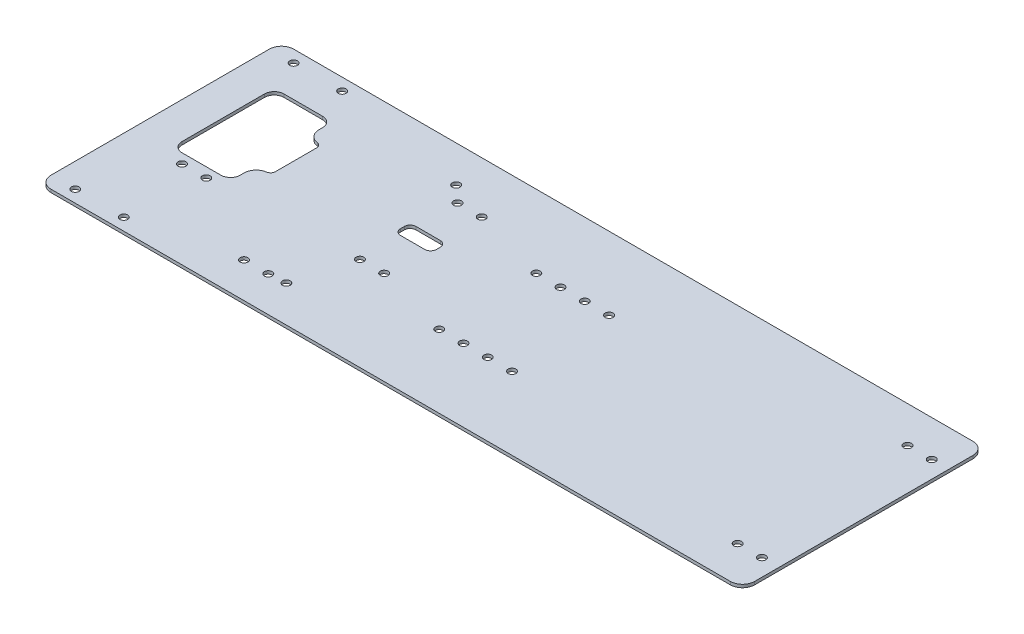
SolidWorks part; units mm, degrees
ref_plane "Front Plane" through (0, 0, 0) normal (0, 0, 1) x (1, 0, 0)
ref_plane "Top Plane" through (0, 0, 0) normal (0, 1, 0) x (1, 0, 0)
ref_plane "Right Plane" through (0, 0, 0) normal (1, 0, 0) x (0, 0, -1)
sketch "Sketch1" plane through (0, 0, 0) normal (0, 1, 0) x (1, 0, 0)
  line L0 (128.27, 0) -> (-128.27, 0) construction
  line L1 (184.15, 63.5) -> (-184.15, 63.5)
  line L2 (184.15, 63.5) -> (184.15, -63.5)
  line L3 (184.15, -63.5) -> (-184.15, -63.5)
  line L4 (-184.15, 63.5) -> (-184.15, -63.5)
  line L5 (184.15, 63.5) -> (-184.15, -63.5) construction
  line L6 (184.15, -63.5) -> (-184.15, 63.5) construction
  line L7 (-128.27, 0) -> (-128.27, 31.75) construction
  line L8 (-128.27, 31.75) -> (-134.62, 31.75) construction
  line L9 (-128.27, 6.35) -> (-134.62, 6.35) construction
  line L12 (-165.1, -12.7) -> (-165.1, 40.64)
  line L15 (-134.62, -12.7) -> (-165.1, -12.7)
  line L17 (-134.62, 40.64) -> (-165.1, 40.64)
  line L18 (0, 63.5) -> (0, -63.5) construction
  line L19 (-134.62, 40.64) -> (-134.62, -12.7)
  line L21 (-95.25, -45.0215) -> (-95.25, -32.3215) construction
  line L22 (-82.55, -45.0215) -> (-95.25, -45.0215) construction
  line L25 (128.27, 31.75) -> (128.27, 6.35) construction
  line L26 (-95.25, -32.3215) -> (-82.55, -32.3215) construction
  line L30 (-82.55, -32.3215) -> (-82.55, -45.0215) construction
  line L31 (184.15, -17.78) -> (154.94, -17.78) construction
  line L32 (146.05, 57.15) -> (184.15, 57.15) construction
  line L33 (154.94, -17.78) -> (142.24, -17.78) construction
  line L34 (146.05, -57.15) -> (184.15, -57.15) construction
  line L35 (-146.05, -57.15) -> (-184.15, -57.15) construction
  line L36 (-146.05, 57.15) -> (-184.15, 57.15) construction
  line L37 (-128.27, 0) -> (-128.27, 6.35) construction
  line L38 (-184.15, -17.78) -> (-154.94, -17.78) construction
  line L39 (-154.94, -17.78) -> (-142.24, -17.78) construction
  line L40 (-134.62, 27.305) -> (-127, 27.305)
  line L41 (-127, 27.305) -> (-127, 0.635)
  line L42 (-127, 0.635) -> (-134.62, 0.635)
  circle A4 centre (171.45, 31.75) radius 2.032 construction
  circle A5 centre (128.27, 31.75) radius 2.032 construction
  circle A6 centre (128.27, 6.35) radius 2.032 construction
  circle A7 centre (171.45, -3.81) radius 2.032 construction
  circle A8 centre (171.45, -57.15) radius 2.032
  circle A9 centre (146.05, -57.15) radius 2.032
  circle A10 centre (171.45, 57.15) radius 2.032
  circle A11 centre (146.05, 57.15) radius 2.032
  circle A12 centre (-146.05, -57.15) radius 2.032
  circle A13 centre (-171.45, -57.15) radius 2.032
  circle A14 centre (-146.05, 57.15) radius 2.032
  circle A15 centre (-171.45, 57.15) radius 2.032
  circle A16 centre (142.24, -17.78) radius 2.032 construction
  circle A17 centre (154.94, -17.78) radius 2.032 construction
  circle A18 centre (-154.94, -17.78) radius 2.032
  circle A19 centre (-142.24, -17.78) radius 2.032
  circle A20 centre (-95.25, -45.0215) radius 2.032
  circle A21 centre (-82.55, -45.0215) radius 2.032
  circle A22 centre (-95.25, -32.3215) radius 2.032
  circle A23 centre (-82.55, -32.3215) radius 2.032
  point P0 (0, 0)
  point P11 (-128.27, 0)
  point P13 (-134.62, 31.75)
  point P17 (-134.62, 6.35)
  point P37 (0, 0)
  point P50 (171.45, 57.15)
  point P51 (146.05, 57.15)
  point P56 (171.45, -57.15)
  point P57 (146.05, -57.15)
  point P84 (-130.81, 27.305)
  point P87 (130.81, 27.305)
  dimension "D5" = 13.335
  dimension "D18" = 4.064
  dimension "D1" = 368.3
  dimension "D2" = 127
  dimension "D3" = 128.27
  dimension "D4" = 25.4
  dimension "D7" = 6.35
  dimension "D8" = 30.48
  dimension "D9" = 53.34
  dimension "D10" = 8.89
  dimension "D11" = 19.05
  dimension "D14" = 12.7
  dimension "D15" = 38.1
  dimension "D16" = 12.7
  dimension "D17" = 38.1
  dimension "D19" = 31.75
  dimension "D20" = 6.35
  dimension "D21" = 6.35
  dimension "D22" = 5.08
  dimension "D23" = 29.21
  dimension "D24" = 12.7
  dimension "D25" = 88.9
  dimension "D26" = 12.7
  dimension "D27" = 7.62
  dimension "D28" = 26.67
  dimension "D29" = 13.335
  dimension "D30" = 18.4785
  dimension "D31" = 12.7
extrude "Boss-Extrude1" add sketch "Sketch1" along normal blind 1.5875 contours L1 L4 L3 L2 A23 A22 A21 A20 A18 A14 A12 A11 A10 A9 A8 L41 L42 L19 L15 L12 L17 L40 A13 A15 A19 | A9 | A8 | A11 | A10 | A22 | A23 region at (6.2259, 0, 0.5157) region at (171.45, 0, 57.15) region at (146.05, 0, 57.15) region at (171.45, 0, -57.15) region at (146.05, 0, -57.15) region at (-95.25, 0, 32.3215) region at (-82.55, 0, 32.3215)
sketch "Sketch2" [suppressed] plane through (0, 1.5875, 0) normal (0, 1, 0) x (1, 0, 0)
  line L0 (-69.85, 63.5) -> (-69.85, -63.5)
  line L1 (184.15, 63.5) -> (-184.15, 63.5) construction
  line L2 (184.15, -63.5) -> (-184.15, -63.5) construction
  circle A0 centre (-82.55, -45.0215) radius 2.032 construction
  circle M9 centre (146.05, 57.15) radius 2.032
  circle M10 centre (171.45, 57.15) radius 2.032
  circle M11 centre (146.05, -57.15) radius 2.032
  circle M12 centre (171.45, -57.15) radius 2.032
  line M13 (184.15, 63.5) -> (-184.15, 63.5)
  line M15 (-184.15, -63.5) -> (184.15, -63.5)
  line M16 (184.15, -63.5) -> (184.15, 63.5)
  dimension "D1" = 12.7
extrude "Cut-Extrude1" [suppressed] cut sketch "Sketch2" against normal through all flip side to cut contours L0 M13 M15 M16 M10 M12 M11 M9
fillet "Fillet1" radius 5.08 4 edges at (-134.62, 0.7937, 12.7) (-165.1, 0.7937, 12.7) (-165.1, 0.7937, -40.64) (-134.62, 0.7937, -40.64)
fillet "Fillet3" radius 6.35 4 edges at (184.15, 0.7937, 63.5) (184.15, 0.7937, -63.5) (-184.15, 0.7937, 63.5) (-184.15, 0.7937, -63.5)
fillet "Fillet4" radius 2.54 2 edges at (-127, 0.7937, -0.635) (-127, 0.7937, -27.305)
fillet "Fillet5" radius 6.35 2 edges at (-134.62, 0.7937, -0.635) (-134.62, 0.7937, -27.305)
fillet "Fillet6" [suppressed] radius 6.35
sketch "Sketch3" plane through (0, 1.5875, 0) normal (0, 1, 0) x (1, 0, 0)
  circle A0 centre (-12.7, -25.4) radius 2.032 construction
  arc A1 (1.9352, -24.7804) -> (1.9352, -26.0196) centre (0, -25.4) ccw construction
  arc A2 (10.7648, -26.0196) -> (10.7648, -24.7804) centre (12.7, -25.4) ccw construction
  circle A3 centre (25.4, -25.4) radius 2.032 construction
  circle A4 centre (25.4, 25.4) radius 2.032 construction
  arc A5 (10.7648, 24.7804) -> (10.7648, 26.0196) centre (12.7, 25.4) ccw construction
  arc A6 (1.9352, 26.0196) -> (1.9352, 24.7804) centre (0, 25.4) ccw construction
  circle A7 centre (-12.7, 25.4) radius 2.032 construction
  circle A9 centre (162.56, -44.45) radius 2.032 construction
  circle A10 centre (162.56, 44.45) radius 2.032 construction
  circle A11 centre (-73.66, 44.45) radius 2.032 construction
  circle A13 centre (-73.66, -44.45) radius 2.032 construction
  circle A14 centre (-12.7, -25.4) radius 2.032
  arc A15 (1.9352, -24.7804) -> (1.9352, -26.0196) centre (0, -25.4) ccw
  arc A16 (10.7648, -26.0196) -> (10.7648, -24.7804) centre (12.7, -25.4) ccw
  circle A17 centre (25.4, -25.4) radius 2.032
  circle A18 centre (25.4, 25.4) radius 2.032
  arc A19 (10.7648, 24.7804) -> (10.7648, 26.0196) centre (12.7, 25.4) ccw
  arc A20 (1.9352, 26.0196) -> (1.9352, 24.7804) centre (0, 25.4) ccw
  circle A21 centre (-12.7, 25.4) radius 2.032
  circle A23 centre (162.56, -44.45) radius 2.032
  circle A24 centre (162.56, 44.45) radius 2.032
  circle A25 centre (-73.66, 44.45) radius 2.032
  circle A27 centre (-73.66, -44.45) radius 2.032
  circle A28 centre (0, -25.4) radius 2.032
  circle A29 centre (12.7, -25.4) radius 2.032
  circle A30 centre (0, 25.4) radius 2.032
  circle A31 centre (12.7, 25.4) radius 2.032
  circle A32 centre (175.26, 44.45) radius 2.032 construction
  circle A33 centre (175.26, -44.45) radius 2.032 construction
  circle A34 centre (175.26, 44.45) radius 2.032
  circle A35 centre (175.26, -44.45) radius 2.032
extrude "Cut-Extrude5" cut sketch "Sketch3" against normal through all contours A24 | A15 A28 | A16 A29 | A20 A30 | A19 A31 | A27 | A25 | A21 | A14 | A17 | A18 | A23 | A35 | A34 region at (0, 1.5875, 25.4) region at (12.7, 1.5875, 25.4) region at (12.7, 1.5875, -25.4) region at (0, 1.5875, -25.4) region at (162.56, 1.5875, -44.45)
sketch "Sketch4" plane through (0, 1.5875, 0) normal (0, 1, 0) x (1, 0, 0)
  line L0 (-50.9125, -11.9075) -> (-66.7875, -11.9075) construction
  line L1 (-66.7875, -17.0193) -> (-50.9125, -17.0193) construction
  line L2 (-66.7875, 38.758) -> (-50.9125, 38.758) construction
  line L3 (-50.9125, 34.44) -> (-66.7875, 34.44) construction
  line L4 (-50.9125, -11.9075) -> (-66.7875, -11.9075)
  line L5 (-66.7875, -17.0193) -> (-50.9125, -17.0193)
  line L6 (-66.7875, 38.758) -> (-50.9125, 38.758)
  line L7 (-50.9125, 34.44) -> (-66.7875, 34.44)
  line L8 (-66.7875, 36.599) -> (-50.9125, 36.599) construction
  line L9 (-66.7875, -14.4634) -> (-50.9125, -14.4634) construction
  arc A0 (-50.9125, -17.0193) -> (-50.9125, -11.9075) centre (-50.9125, -14.4634) ccw construction
  arc A1 (-66.7875, -11.9075) -> (-66.7875, -17.0193) centre (-66.7875, -14.4634) ccw construction
  arc A3 (-66.7875, 38.758) -> (-66.7875, 34.44) centre (-66.7875, 36.599) ccw construction
  arc A4 (-50.9125, -17.0193) -> (-50.9125, -11.9075) centre (-50.9125, -14.4634) ccw
  arc A5 (-66.7875, -11.9075) -> (-66.7875, -17.0193) centre (-66.7875, -14.4634) ccw
  arc A6 (-50.9125, 34.44) -> (-50.9125, 38.758) centre (-50.9125, 36.599) ccw construction
  arc A7 (-66.7875, 38.758) -> (-66.7875, 34.44) centre (-66.7875, 36.599) ccw
  arc A8 (-50.9125, 34.44) -> (-50.9125, 38.758) centre (-50.9125, 36.599) ccw
  circle A9 centre (-65.1365, 36.599) radius 2.032
  circle A10 centre (-52.4365, 36.599) radius 2.032
  circle A11 centre (-65.1365, -14.4634) radius 2.032
  circle A12 centre (-52.4365, -14.4634) radius 2.032
  dimension "D1" = 4.064
  dimension "D2" = 12.7
  dimension "D3" = 1.651
  dimension "D4" = 12.7
  dimension "D5" = 1.651
extrude "Cut-Extrude6" cut sketch "Sketch4" against normal through all and the other way through all contours A11 | A12 | A10 | A9 region at (-65.1365, 1.5875, -36.599) region at (-52.4365, 1.5875, -36.599) region at (-65.1365, 1.5875, 14.4634) region at (-52.4365, 1.5875, 14.4634)
sketch "Sketch5" plane through (0, 1.5875, 0) normal (0, 1, 0) x (1, 0, 0)
  line L1 (-67.175, 12.0678) -> (-67.175, 10.0678) construction
  line L3 (-67.175, 12.0678) -> (-67.175, 10.0678)
  line L4 (-65.375, 13.8678) -> (-52.675, 13.8678)
  line L5 (-65.375, 8.2678) -> (-52.675, 8.2678)
  line L6 (-50.8769, 10.013) -> (-50.8769, 12.0776)
  line L11 (-65.375, 6.9978) -> (-52.6746, 6.9978)
  line L12 (-49.6069, 9.9962) -> (-49.6069, 12.0806)
  line L13 (-65.375, 15.1378) -> (-52.6743, 15.1378)
  line L14 (-68.445, 12.0678) -> (-68.445, 10.0678)
  arc A0 (-63.575, 12.0678) -> (-67.175, 12.0678) centre (-65.375, 12.0678) ccw construction
  arc A2 (-67.175, 10.0678) -> (-65.375, 8.2678) centre (-65.375, 10.0678) ccw construction
  arc A3 (-65.375, 13.8678) -> (-67.175, 12.0678) centre (-65.375, 12.0678) ccw
  arc A5 (-67.175, 10.0678) -> (-65.375, 8.2678) centre (-65.375, 10.0678) ccw
  arc A6 (-50.8769, 12.0776) -> (-52.675, 13.8678) centre (-52.6769, 12.0678) ccw
  arc A7 (-52.675, 8.2678) -> (-50.8769, 10.013) centre (-52.6761, 10.0678) ccw
  arc A12 (-52.6746, 6.9978) -> (-49.6069, 9.9962) centre (-52.6761, 10.0678) ccw
  arc A13 (-49.6069, 12.0806) -> (-52.6743, 15.1378) centre (-52.6769, 12.0678) ccw
  arc A14 (-65.375, 15.1378) -> (-68.445, 12.0678) centre (-65.375, 12.0678) ccw
  arc A15 (-68.445, 10.0678) -> (-65.375, 6.9978) centre (-65.375, 10.0678) ccw
  point P0 (-52.2707, 13.8678)
  point P11 (-52.6734, 8.2678)
  point P17 (0, 0)
  point P18 (0, 0)
  point P19 (-45.6628, 8.2678)
  point P20 (-52.6746, 8.2678)
  point P21 (-52.6749, 8.2678)
  point P22 (-54.4744, 10.0678)
  point P23 (-54.4746, 12.0678)
  point P24 (-50.8758, 10.0678)
  point P25 (-50.8758, 12.0678)
  point P26 (-54.4724, 12.0678)
  point P27 (-52.675, 12.0738)
  point P28 (-52.675, 12.0798)
  point P29 (-52.6761, 10.0039)
  dimension "D1" = 16.2981
  dimension "D2" = 12.7
  dimension "D3" = 2.0646
  dimension "D4" = 1.7902
  dimension "D6" = 1.27
extrude "Cut-Extrude7" cut sketch "Sketch5" against normal through all and the other way through all contours L14 A15 L11 A12 L12 A13 L13 A14 A7 L5 A5 L3 A3 L4 A6 L6 | L5 A7 L6 A6 L4 A3 L3 A5 region at (-59.0258, 1.5875, -11.0678) region at (-67.4007, 1.5875, -8.0421)
equation "\".80.55in\"=0.55"
